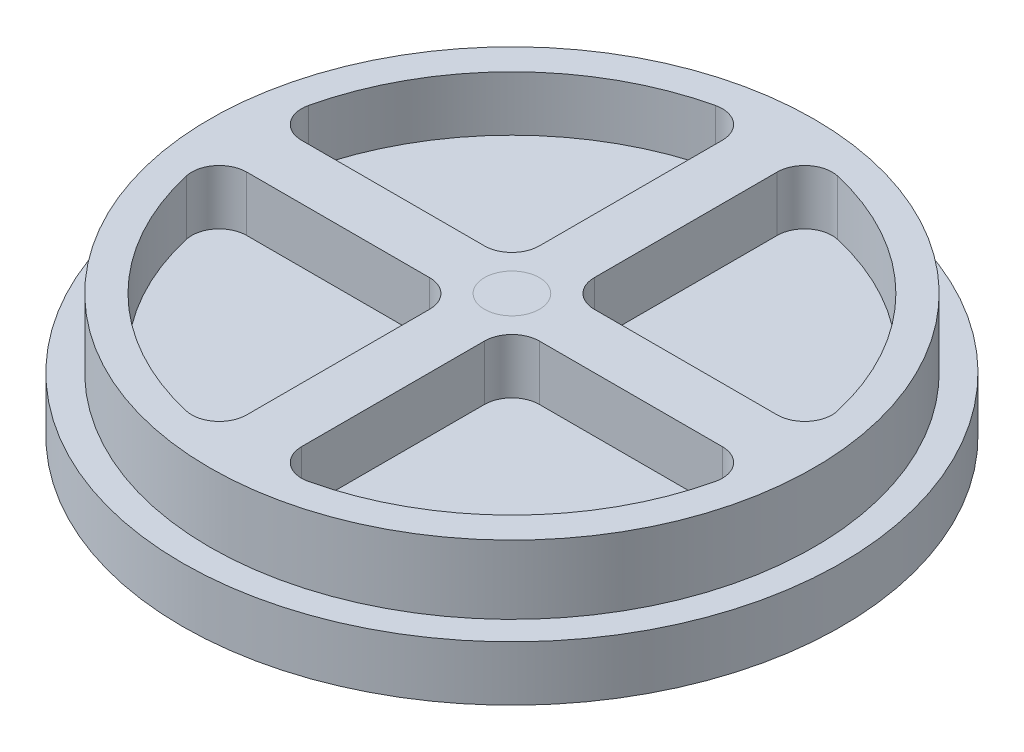
SolidWorks part; units mm, degrees
ref_plane "Front Plane" through (0, 0, 0) normal (0, 0, 1) x (1, 0, 0)
ref_plane "Top Plane" through (0, 0, 0) normal (0, 1, 0) x (1, 0, 0)
ref_plane "Right Plane" through (0, 0, 0) normal (1, 0, 0) x (0, 0, -1)
sketch "Sketch1" plane through (0, 0, 0) normal (0, 1, 0) x (1, 0, 0)
  circle A0 centre (0, 0) radius 304.8
  circle A1 centre (0, 0) radius 25.4
  dimension "D1" = 609.6
  dimension "D2" = 50.8
extrude "Boss-Extrude1" add sketch "Sketch1" against normal blind 50.8 contours A1 | A0 A1 region at (-296.179, 0, 0) region at (0, 0, 0)
extrude "Boss-Extrude6" add sketch "Sketch1<6>" along normal blind 63.5 contours A1 region at (0, 0, 0)
sketch "Sketch1<6>" plane through (0, 0, 0) normal (0, 1, 0) x (1, 0, 0) same geometry as "Sketch1"
extrude "Boss-Extrude4" add sketch "Sketch1<5>" along normal blind 50.8 contours A1 region at (0, 0, 0)
sketch "Sketch1<5>" plane through (0, 0, 0) normal (0, 1, 0) x (1, 0, 0) same geometry as "Sketch1"
sketch "Sketch5" plane through (0, 0, 0) normal (0, 1, 0) x (1, 0, 0)
  circle A0 centre (0, 0) radius 279.4
  circle A1 centre (0, 0) radius 25.4
  dimension "D1" = 558.8
  dimension "D2" = 50.8
extrude "Boss-Extrude5" add sketch "Sketch5" along normal blind 12.7 separate body
sketch "Sketch6" plane through (0, 12.7, 0) normal (0, 1, 0) x (1, 0, 0)
  line L0 (0, 0) -> (0, -279.4) construction
  line L1 (0, 0) -> (-279.4, 0) construction
  line L4 (-25.4, -219.9121) -> (-25.4, -50.8)
  line L5 (-50.8, -25.4) -> (-219.9121, -25.4)
  line L6 (-219.9121, 25.4) -> (-50.8, 25.4)
  line L7 (-25.4, 50.8) -> (-25.4, 219.9121)
  line L8 (25.4, 219.9121) -> (25.4, 50.8)
  line L9 (50.8, 25.4) -> (219.9121, 25.4)
  line L10 (219.9121, -25.4) -> (50.8, -25.4)
  line L11 (25.4, -50.8) -> (25.4, -219.9121)
  circle A1 centre (0, 0) radius 279.4 construction
  arc A5 (-56.5169, -244.6604) -> (-244.6604, -56.5169) centre (0, 0) cw
  arc A6 (-244.6604, -56.5169) -> (-219.9121, -25.4) centre (-219.9121, -50.8) cw
  arc A7 (-56.5169, -244.6604) -> (-25.4, -219.9121) centre (-50.8, -219.9121) ccw
  arc A8 (-50.8, -25.4) -> (-25.4, -50.8) centre (-50.8, -50.8) cw
  arc A9 (-244.6604, 56.5169) -> (-56.5169, 244.6604) centre (0, 0) cw
  arc A10 (-56.5169, 244.6604) -> (-25.4, 219.9121) centre (-50.8, 219.9121) cw
  arc A11 (-25.4, 50.8) -> (-50.8, 25.4) centre (-50.8, 50.8) cw
  arc A12 (-244.6604, 56.5169) -> (-219.9121, 25.4) centre (-219.9121, 50.8) ccw
  arc A13 (56.5169, 244.6604) -> (244.6604, 56.5169) centre (0, 0) cw
  arc A14 (244.6604, 56.5169) -> (219.9121, 25.4) centre (219.9121, 50.8) cw
  arc A15 (50.8, 25.4) -> (25.4, 50.8) centre (50.8, 50.8) cw
  arc A16 (56.5169, 244.6604) -> (25.4, 219.9121) centre (50.8, 219.9121) ccw
  arc A17 (244.6604, -56.5169) -> (56.5169, -244.6604) centre (0, 0) cw
  arc A18 (56.5169, -244.6604) -> (25.4, -219.9121) centre (50.8, -219.9121) cw
  arc A19 (25.4, -50.8) -> (50.8, -25.4) centre (50.8, -50.8) cw
  arc A20 (244.6604, -56.5169) -> (219.9121, -25.4) centre (219.9121, -50.8) ccw
  circle M1 centre (0, 0) radius 279.4
  circle M2 centre (0, 0) radius 25.4
  dimension "D1" = 25.4
  dimension "D2" = 25.4
  dimension "D3" = 251.1033
  dimension "D4" = 25.4
  dimension "D5" = 4
extrude "Boss-Extrude7" add sketch "Sketch6" along normal blind 50.8 separate body contours A20 A17 A18 L11 A19 L10 A16 A13 A14 L9 A15 L8 A12 A9 A10 L7 A11 L6 L5 A8 L4 A7 A5 A6 M1 M2 region at (-271.4974, 12.7, 0)
combine bodies "Combine1" operation type add bodies to combine 108 105
